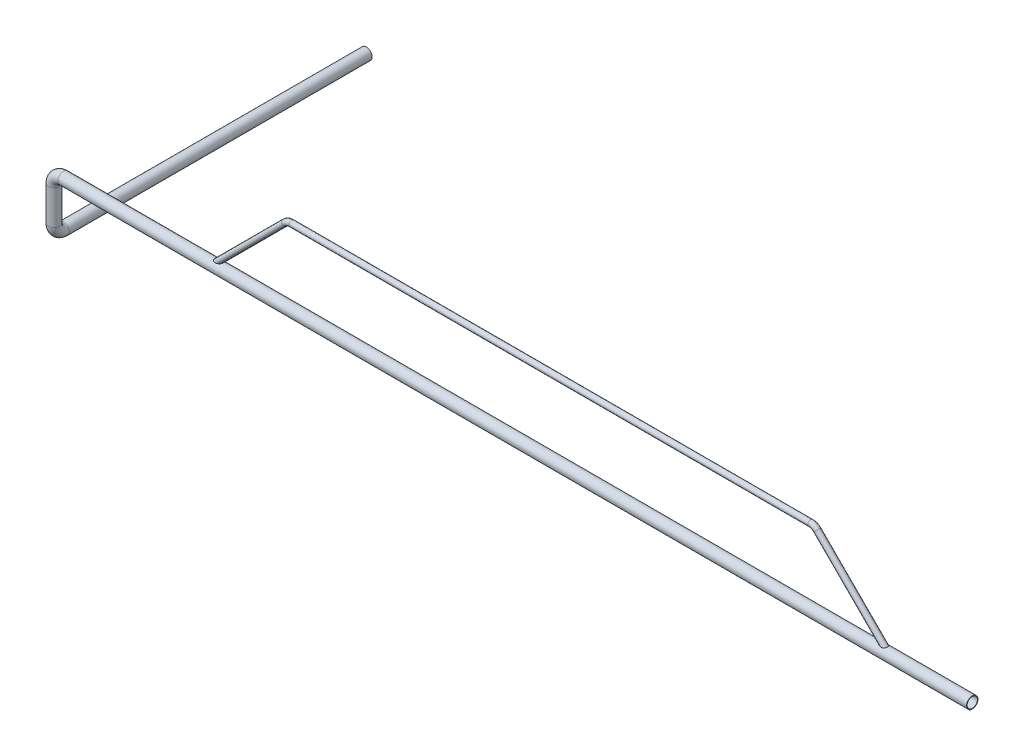
SolidWorks part; units mm, degrees
ref_plane "Plano frontal" through (0, 0, 0) normal (0, 0, 1) x (1, 0, 0)
ref_plane "Plano superior" through (0, 0, 0) normal (0, 1, 0) x (1, 0, 0)
ref_plane "Plano direito" through (0, 0, 0) normal (1, 0, 0) x (0, 0, -1)
sketch3d "3DSketch1"
  line L0 (-24718.7732, -8334.1163, 40483.3235) -> (-29492.9056, -8334.1163, 40483.3235)
  line L1 (-29542.9056, -8384.1163, 40483.3235) -> (-29542.9056, -8564.5277, 40483.3235)
  line L2 (-29542.9056, -8614.5277, 40433.3235) -> (-29542.9056, -8614.5277, 38842.1132)
  circle A0 centre (-24718.7732, -8334.1163, 40483.3235) radius 26.2509 construction
  arc A1 (-29542.9056, -8564.5277, 40483.3235) -> (-29542.9056, -8614.5277, 40433.3235) centre (-29542.9056, -8564.5277, 40433.3235) ccw
  arc A2 (-29542.9056, -8384.1163, 40483.3235) -> (-29492.9056, -8334.1163, 40483.3235) centre (-29492.9056, -8384.1163, 40483.3235) ccw
  point P4 (-24692.5223, -8334.1163, 40483.3235)
  point P7 (-29542.9056, -8614.5277, 38842.1132)
  point P11 (-29542.9056, -8614.5277, 40483.3235)
  point P12 (-29492.9056, -8564.5277, 40433.3235)
  point P15 (-29542.9056, -8334.1163, 40483.3235)
  point P16 (-29492.9056, -8384.1163, 40433.3235)
  dimension "D1" = 50
sweep "Sweep-Thin1" add path "3DSketch1" circular profile diameter 60 parameters "D1"=3, "D3"=60
sketch3d "3DSketch3"
  line L0 (-25155.2757, -8334.1163, 40483.3235) -> (-25532.845, -7956.547, 40483.3235)
  line L1 (-24718.7732, -8334.1163, 40483.3235) -> (-29492.9056, -8334.1163, 40483.3235) construction
  line L2 (-25568.2003, -7941.9024, 40483.3235) -> (-28294.322, -7941.9024, 40483.3235)
  line L3 (-28329.6773, -7956.547, 40483.3235) -> (-28707.2466, -8334.1163, 40483.3235)
  line L4 (-25547.4897, -7941.9024, 40483.3235) -> (-25547.4897, -8334.1163, 40483.3235) construction
  arc A0 (-25568.2003, -7941.9024, 40483.3235) -> (-25532.845, -7956.547, 40483.3235) centre (-25568.2003, -7991.9024, 40483.3235) ccw
  arc A1 (-28294.322, -7941.9024, 40483.3235) -> (-28329.6773, -7956.547, 40483.3235) centre (-28294.322, -7991.9024, 40483.3235) ccw
  point P7 (0, 0, 0)
  point P8 (-25408.4462, -7972.1292, 40483.3235)
  point P9 (-25547.4897, -7941.9024, 40483.3235)
  point P10 (-27346.8321, -7941.9024, 40483.3235)
  point P11 (-28326.9672, -7941.9024, 40483.3235)
  point P12 (-28315.0327, -7941.9024, 40483.3235)
  point P15 (-25547.4897, -7941.9024, 40483.3235)
  point P17 (-25568.2003, -7991.9024, 40433.3235)
  point P20 (-28315.0327, -7941.9024, 40483.3235)
  point P21 (-28294.322, -7991.9024, 40533.3235)
  dimension "D3" = 50
  dimension "D1" = 135
  dimension "D2" = 135
sweep "Sweep-Thin2" add path "3DSketch3" circular profile diameter 30 parameters "D1"=3, "D3"=30
